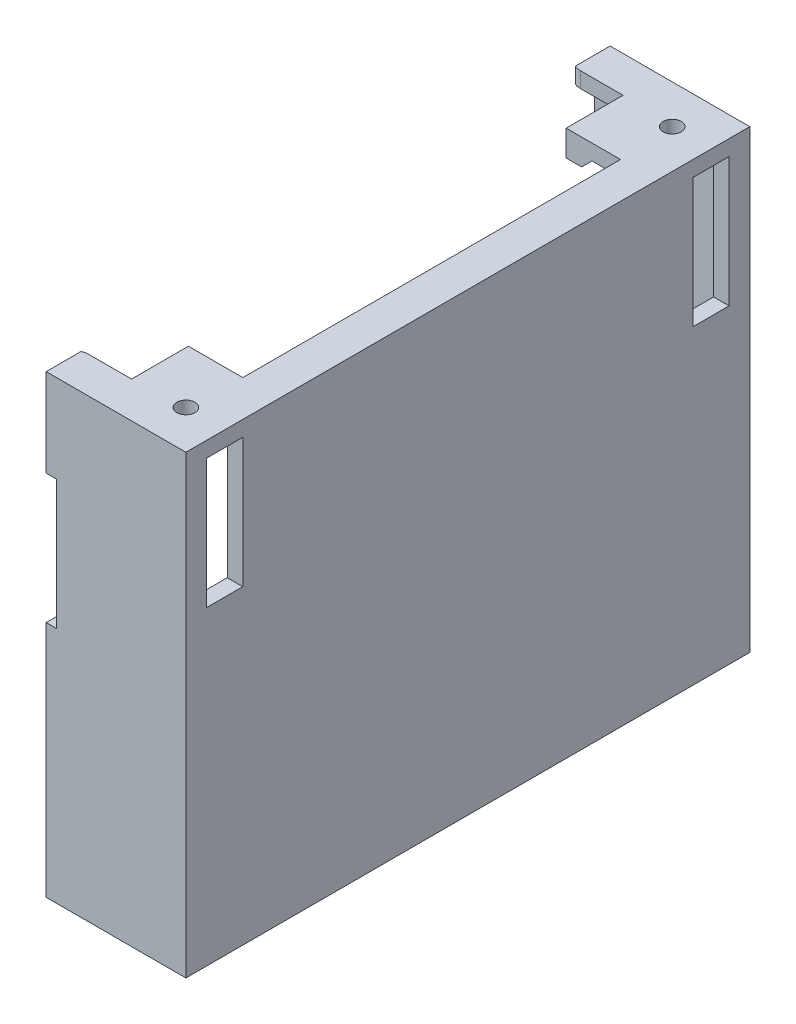
SolidWorks part; units mm, degrees
ref_plane "Front Plane" through (0, 0, 0) normal (0, 0, 1) x (1, 0, 0)
ref_plane "Top Plane" through (0, 0, 0) normal (0, 1, 0) x (1, 0, 0)
ref_plane "Right Plane" through (0, 0, 0) normal (1, 0, 0) x (0, 0, -1)
sketch "Sketch1" plane through (0, 0, 0) normal (0, 1, 0) x (1, 0, 0)
  line L1 (-21.25, -47) -> (21.25, -47) construction
  line L2 (-21.25, -47) -> (-21.25, 47) construction
  line L3 (-21.25, 47) -> (21.25, 47) construction
  line L4 (21.25, -47) -> (21.25, 47) construction
  line L5 (-21.25, -47) -> (21.25, 47) construction
  line L6 (-21.25, 47) -> (21.25, -47) construction
  line L7 (-28.75, -54.5) -> (28.75, -54.5)
  line L8 (-28.75, -54.5) -> (-28.75, 54.5)
  line L9 (-28.75, 54.5) -> (28.75, 54.5)
  line L10 (28.75, -54.5) -> (28.75, 54.5)
  line L11 (-28.75, -54.5) -> (28.75, 54.5) construction
  line L12 (-28.75, 54.5) -> (28.75, -54.5) construction
  line L13 (-14.25, -47.5) -> (14.25, -47.5)
  line L14 (-14.25, -47.5) -> (-14.25, 47.5)
  line L15 (-14.25, 47.5) -> (14.25, 47.5)
  line L16 (14.25, -47.5) -> (14.25, 47.5)
  line L17 (-14.25, -47.5) -> (14.25, 47.5) construction
  line L18 (-14.25, 47.5) -> (14.25, -47.5) construction
  circle A0 centre (-21.25, 47) radius 1.75
  circle A1 centre (21.25, 47) radius 1.75
  circle A2 centre (21.25, -47) radius 1.75
  circle A3 centre (-21.25, -47) radius 1.75
  point P0 (0, 0)
  point P4 (0, 0)
  point P11 (0, 0)
  dimension "D1" = 94
  dimension "D2" = 42.5
  dimension "D3" = 3.5
  dimension "D4" = 3.5
  dimension "D5" = 3.5
  dimension "D6" = 3.5
  dimension "D7" = 7.5
  dimension "D8" = 7.5
  dimension "D9" = 7
  dimension "D10" = 7
extrude "Boss-Extrude1" add sketch "Sketch1" along normal mid plane 3
sketch "Sketch3" plane through (0, 1.5, 0) normal (0, 1, 0) x (1, 0, 0)
  line L0 (28.75, -54.5) -> (28.75, 54.5) construction
  line L1 (-21.75, -40.5) -> (21.75, -40.5)
  line L2 (-21.75, -40.5) -> (-21.75, 40.5)
  line L3 (-21.75, 40.5) -> (21.75, 40.5)
  line L4 (21.75, -40.5) -> (21.75, 40.5)
  line L5 (-21.75, -40.5) -> (21.75, 40.5) construction
  line L6 (-21.75, 40.5) -> (21.75, -40.5) construction
  line L7 (14.25, 47.5) -> (-14.25, 47.5) construction
  point P0 (0, 0)
  dimension "D1" = 7
  dimension "D2" = 7
extrude "Cut-Extrude1" cut sketch "Sketch3" against normal blind 3
sketch "Sketch4" plane through (0, -1.5, 0) normal (0, -1, 0) x (1, 0, 0)
  line L0 (28.75, -54.5) -> (-28.75, -54.5) construction
  line L1 (28.75, 54.5) -> (27.3046, 54.5)
  line L2 (28.75, 54.5) -> (28.75, -54.5)
  line L3 (28.75, -54.5) -> (27.3046, -54.5)
  line L4 (25.75, 51.5) -> (25.75, -51.5)
  line L5 (-28.75, -54.5) -> (-28.75, 54.5) construction
  line L6 (27.3046, -54.5) -> (-28.75, -54.5)
  line L8 (25.75, -51.5) -> (-28.75, -51.5)
  line L9 (-28.75, -54.5) -> (-28.75, -51.5)
  line L11 (-28.75, 54.5) -> (27.3046, 54.5)
  line L12 (-28.75, 54.5) -> (-28.75, 51.5)
  line L13 (-28.75, 51.5) -> (25.75, 51.5)
  dimension "D1" = 3
  dimension "D2" = 3
  dimension "D3" = 3
extrude "Boss-Extrude2" add sketch "Sketch4" along normal blind 85
sketch "Sketch5" plane through (0, 0, 0) normal (1, 0, 0) x (0, 0, -1)
  line L1 (-65.4259, 8.614) -> (79.965, 8.614)
  line L2 (-65.4259, 8.614) -> (-65.4259, -117.24)
  line L3 (-65.4259, -117.24) -> (79.965, -117.24)
  line L4 (79.965, 8.614) -> (79.965, -117.24)
extrude "Cut-Extrude2" cut sketch "Sketch5" against normal blind 85
sketch "Sketch6" plane through (0, 0, 51.5) normal (0, 0, -1) x (-1, 0, 0)
  line L0 (0, -6.5) -> (-20.75, -27.25)
  line L1 (0, -86.5) -> (0, 1.5) construction
  line L2 (-20.75, -27.25) -> (-20.75, -57.75)
  line L4 (0, -86.5) -> (-28.75, -86.5) construction
  line L5 (0, -78.5) -> (0, -6.5)
  line L6 (-25.75, -1.5) -> (0, -1.5) construction
  line L7 (-25.75, -86.5) -> (-25.75, -1.5) construction
  line L8 (0, -78.5) -> (-20.75, -57.75)
  dimension "D1" = 45
  dimension "D2" = 5
  dimension "D3" = 5
  dimension "D4" = 8
  dimension "D5" = 45
extrude "Cut-Extrude3" cut sketch "Sketch6" along normal through all
sketch "Sketch8" plane through (25.75, 0, 0) normal (-1, 0, 0) x (0, 0, 1)
  line L0 (51.5, -27.25) -> (51.5, -86.5) construction
  line L1 (-51.5, -86.5) -> (51.5, -86.5)
  line L2 (-51.5, -86.5) -> (-51.5, -83.5)
  line L3 (-51.5, -83.5) -> (51.5, -83.5)
  line L4 (51.5, -86.5) -> (51.5, -83.5)
  dimension "D1" = 3
extrude "Boss-Extrude3" add sketch "Sketch8" along normal up to surface (25.75 mm away) up to face at (0, -2.1667, -51.1667)
fillet "Fillet3" radius 3 10 edges at (0, 0, 47.5) (14.25, 0, 47.5) (21.75, 0, 40.5) (0, -6.5, -53) (0, -78.5, -53) (20.75, -57.75, -53) (20.75, -27.25, -53) (0, 0, -47.5) (14.25, 0, -47.5) (21.75, 0, -40.5)
sketch "Sketch13" plane through (0, 0, 0) normal (-1, 0, 0) x (0, 0, 1)
  line L1 (-54.5, 1.5) -> (54.5, 1.5)
  line L2 (-54.5, 1.5) -> (-54.5, -86.5)
  line L3 (-54.5, -86.5) -> (54.5, -86.5)
  line L4 (54.5, 1.5) -> (54.5, -86.5)
extrude "Cut-Extrude8" cut sketch "Sketch13" against normal blind 1.75
sketch "Sketch14" plane through (0, 0, 54.5) normal (0, 0, 1) x (1, 0, 0)
  line L0 (1.75, -86.5) -> (1.75, 1.5) construction
  line L1 (1.75, -15.5) -> (3.75, -15.5)
  line L2 (1.75, -15.5) -> (1.75, -40.5)
  line L3 (1.75, -40.5) -> (3.75, -40.5)
  line L4 (3.75, -15.5) -> (3.75, -40.5)
  line L5 (1.75, -1.5) -> (25.75, -1.5) construction
  dimension "D1" = 2
  dimension "D2" = 25
  dimension "D3" = 14
extrude "Cut-Extrude9" cut sketch "Sketch14" against normal blind 5
sketch "Sketch15" plane through (25.75, 0, 0) normal (-1, 0, 0) x (0, 0, 1)
  line L0 (51.5, -1.5) -> (47.7728, -1.5) construction
  line L1 (50.5, -1.5) -> (43.5, -1.5)
  line L2 (50.5, -1.5) -> (50.5, -26.5)
  line L3 (50.5, -26.5) -> (43.5, -26.5)
  line L4 (43.5, -1.5) -> (43.5, -26.5)
  line L6 (48.75, -1.5) -> (48.75, 1.5) construction
  line L9 (0, 0) -> (0, 38.316) construction
  line L10 (-43.5, -1.5) -> (-43.5, -26.5)
  line L11 (-50.5, -26.5) -> (-43.5, -26.5)
  line L12 (-50.5, -1.5) -> (-50.5, -26.5)
  line L13 (-50.5, -1.5) -> (-43.5, -1.5)
  dimension "D1" = 25
  dimension "D2" = 7
  dimension "D3" = 1.75
extrude "Cut-Extrude10" cut sketch "Sketch15" against normal through all
sketch "Sketch16" plane through (0, 1.5, 0) normal (0, 1, 0) x (1, 0, 0)
  line L0 (25.75, 51.5) -> (1.75, 51.5) construction
  line L1 (11.25, 51.5) -> (14.25, 51.5)
  line L2 (11.25, 51.5) -> (11.25, 36.5)
  line L3 (11.25, 36.5) -> (14.25, 36.5)
  line L4 (14.25, 51.5) -> (14.25, 36.5)
  line L5 (0, 0) -> (47.8575, 0) construction
  line L6 (14.25, 40.5) -> (14.25, 44.5) construction
  line L7 (14.25, -51.5) -> (14.25, -36.5)
  line L8 (11.25, -36.5) -> (14.25, -36.5)
  line L9 (11.25, -51.5) -> (11.25, -36.5)
  line L10 (11.25, -51.5) -> (14.25, -51.5)
  dimension "D1" = 3
  dimension "D2" = 15
extrude "Boss-Extrude4" add sketch "Sketch16" against normal blind 5
sketch "Sketch17" plane through (0, 1.5, 0) normal (0, 1, 0) x (1, 0, 0)
  line L0 (21.75, -37.5) -> (21.75, 37.5) construction
  line L1 (14.25, 40.5) -> (21.75, 40.5)
  line L2 (14.25, 40.5) -> (14.25, 36.5)
  line L3 (14.25, 36.5) -> (21.75, 36.5)
  line L4 (21.75, 40.5) -> (21.75, 36.5)
  line L5 (11.25, 36.5) -> (14.25, 36.5) construction
  line L6 (14.25, -36.5) -> (21.75, -36.5)
  line L7 (14.25, -36.5) -> (14.25, -40.5)
  line L8 (14.25, -40.5) -> (21.75, -40.5)
  line L9 (21.75, -36.5) -> (21.75, -40.5)
  line L10 (14.25, -40.5) -> (18.75, -40.5) construction
extrude "Boss-Extrude5" add sketch "Sketch17" against normal blind 3
chamfer "Chamfer1" distance 2 angle 45 2 edges at (14.25, -1.5, -44) (14.25, -1.5, 44)
sketch "Sketch18" plane through (0, -86.5, 0) normal (0, -1, 0) x (1, 0, 0)
  line L0 (1.75, -54.5) -> (1.75, 54.5) construction
  line L1 (28.75, 54.5) -> (1.75, 54.5) construction
  circle A0 centre (1.75, 34.5) radius 10
  dimension "D1" = 20
  dimension "D2" = 20
extrude "Cut-Extrude11" cut sketch "Sketch18" against normal blind 10
